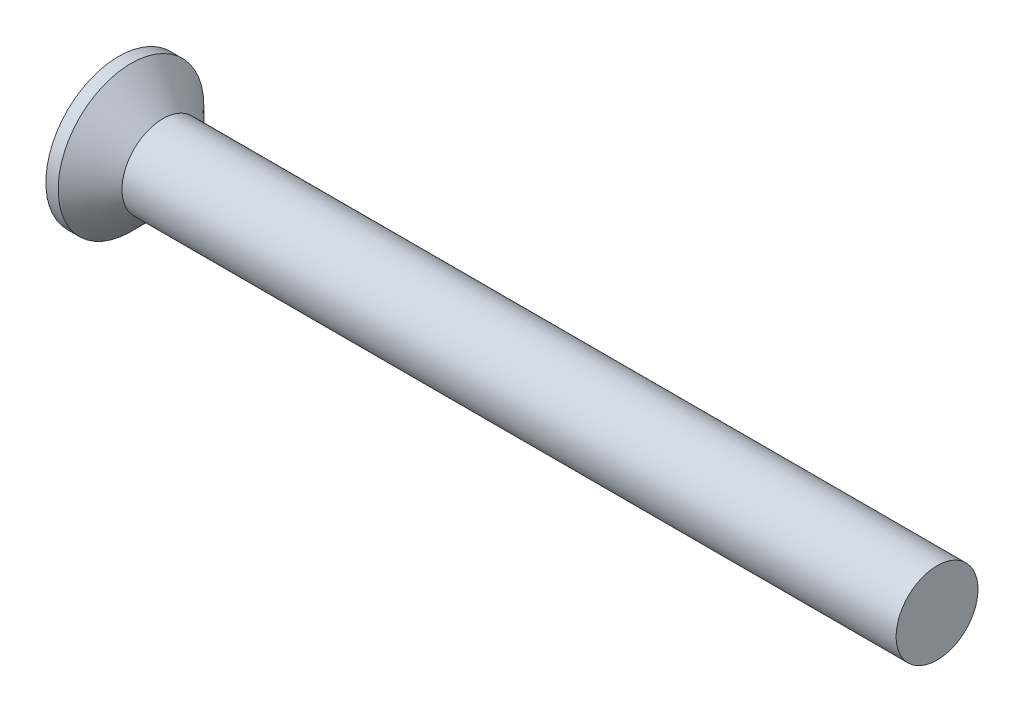
SolidWorks part; units mm, degrees
ref_plane "Front" through (0, 0, 0) normal (0, 0, 1) x (1, 0, 0)
ref_plane "Top" through (0, 0, 0) normal (0, 1, 0) x (1, 0, 0)
ref_plane "Right" through (0, 0, 0) normal (1, 0, 0) x (0, 0, -1)
sketch "Sketch1" plane through (0, 0, 0) normal (0, 0, 1) x (1, 0, 0)
  line L0 (50, 2.5) -> (4.3, 2.5)
  line L1 (4.3, 2.5) -> (2.7, 2.5)
  line L2 (2.7, 2.5) -> (0.75, 4.45)
  line L3 (0.75, 4.45) -> (0, 4.45)
  line L4 (50, 2.5) -> (50, 0)
  line L5 (4.5158, 0) -> (-89.8219, 0) construction
  line L6 (50, 0) -> (0, 0)
  line L7 (0, 4.45) -> (0, 0)
  dimension "D1" = 45
  dimension "dk" = 8.9
  dimension "k" = 2.7
  dimension "l" = 50
  dimension "a" = 1.6
revolve "Base" add sketch "Sketch1" angle 360 about L5
cosmetic thread "ThreadCosmetic1" [suppressed] parameters "bb"=47.3, "THD_MINOR"=4.134
sketch "Sketch6" plane through (0, 0, 0) normal (1, 0, 0) x (0, 0, -1)
  line L0 (-1.9271, 0) -> (2.0512, 0) construction
  line L1 (0, 1.8651) -> (0, -2.0207) construction
  line L2 (0.52, 0.52) -> (0.52, 2.6)
  line L3 (0.52, 2.6) -> (-0.52, 2.6)
  line L4 (-0.52, 0.52) -> (-0.52, 2.6)
  line L5 (0.52, 0.52) -> (2.6, 0.52)
  line L6 (2.6, 0.52) -> (2.6, -0.52)
  line L7 (-2.6, 0.52) -> (-2.6, -0.52)
  line L8 (-0.52, 0.52) -> (-2.6, 0.52)
  line L9 (-0.52, -0.52) -> (-2.6, -0.52)
  line L10 (0.52, -0.52) -> (2.6, -0.52)
  line L11 (-0.52, -0.52) -> (-0.52, -2.6)
  line L12 (0.52, -2.6) -> (-0.52, -2.6)
  line L13 (0.52, -0.52) -> (0.52, -2.6)
  point P16 (-2.6, 0)
  point P17 (2.6, 0)
extrude "CrossRecess" cut sketch "Sketch6" along normal blind 1.35
draft "Draft9" type of draft neutral plane draft angle 30 faces to draft 4 face at (0.675, -2.6, 0) face at (0.675, 0, 2.6) face at (0.675, 0, -2.6) face at (0.675, 2.6, 0) neutral plane through (0, 4.45, 0) neutral plane normal (-1, 0, 0) parameters "D1"=30
fillet "Fillet5" radius 0.3 4 edges at (0.675, -0.52, -0.52) (0.675, -0.52, 0.52) (0.675, 0.52, -0.52) (0.675, 0.52, 0.52)
sketch "Sketch7" plane through (0, 0, 0) normal (1, 0, 0) x (0, 0, -1)
  line L0 (-2.0126, 0) -> (1.9757, 0) construction
  line L1 (0, 1.9314) -> (0, -2.0126) construction
  line L2 (0, 0) -> (1.5555, 1.5555) construction
  line L3 (0, 0.777) -> (1.8385, 1.8385)
  line L4 (-1.5402, 1.5402) -> (0, 0) construction
  line L5 (0.777, 0) -> (1.8385, 1.8385)
  line L6 (0, -0.777) -> (1.8385, -1.8385)
  line L7 (0.777, 0) -> (1.8385, -1.8385)
  line L8 (-0.777, 0) -> (-1.8385, -1.8385)
  line L9 (0, -0.777) -> (-1.8385, -1.8385)
  line L10 (-0.777, 0) -> (-1.8385, 1.8385)
  line L11 (0, 0.777) -> (-1.8385, 1.8385)
  dimension "D3" = 15
extrude "Cut-Extrude3" [suppressed] cut sketch "Sketch7" along normal blind 10 draft 20
sketch "Sketch10" plane through (0, 0, 0) normal (0, 0, 1) x (1, 0, 0)
  line L0 (62.2289, 0) -> (-1.9277, 0) construction
  line L1 (2.7, 2.5) -> (3.5, 2.5)
  line L4 (3.5, 2.5) -> (3.5, 0)
  line L7 (3.5, 0) -> (2.7, 0)
  line L9 (2.7, 2.5) -> (0.75, 4.45) construction
  line L10 (2.7, 2.5) -> (2.7, 0)
  dimension "p" = 0.8
revolve "Revolve2" add sketch "Sketch10" angle 360 about L0
sketch "Sketch8" plane through (0, 0, 0) normal (0, 0, 1) x (1, 0, 0)
  line L0 (12, 2.5) -> (10, 2.067)
  line L1 (10, 2.067) -> (5, 2.067)
  line L3 (50, -2.5) -> (50, 2.5) construction
  line L6 (5, 2.067) -> (5, 7.067)
  line L7 (5, 7.067) -> (12, 7.067)
  line L8 (12, 7.067) -> (12, 2.5)
  line L9 (62.4753, 0) -> (52.9594, 0) construction
  dimension "D1" = 5
  dimension "x" = 2
sketch "Sketch11" plane through (0, 0, 0) normal (0, 0, 1) x (1, 0, 0)
  line L0 (50, 2.125) -> (50.2165, 2.5)
  line L1 (50.2165, 2.5) -> (50.2165, 2.933)
  line L2 (50.2165, 2.933) -> (49.7835, 2.933)
  line L3 (49.7835, 2.933) -> (49.7835, 2.5)
  line L4 (49.7835, 2.5) -> (50, 2.125)
  line L5 (50, -2.5) -> (50, 2.5) construction
  line L6 (0, 0) -> (66.0064, 0) construction
  dimension "D2" = 0.433
revolve "Cut-Revolve10" [suppressed] cut sketch "Sketch11" angle 360 about L6
pattern_linear "LPattern10" [suppressed] count 91 spacing 0.5196 along (-1, 0, 0) of bodies 106
equation "\"D1@Sketch6\" = \"m@Sketch6\" / 5"
equation "\"D1@CrossRecess\" = \"k@Sketch1\" / 2"
equation "\"D1@Sketch11\" = \"d@Sketch1\""
equation "\"D2@Sketch11\" =  ( \"d@Sketch1\" - \"THD_MINOR@ThreadCosmetic1\" )  / 2"
equation "\"D3@LPattern10\" = \"D2@Sketch11\" * 1.2"
equation "\"D1@LPattern10\" = \"bb@ThreadCosmetic1\" / \"D3@LPattern10\" "
